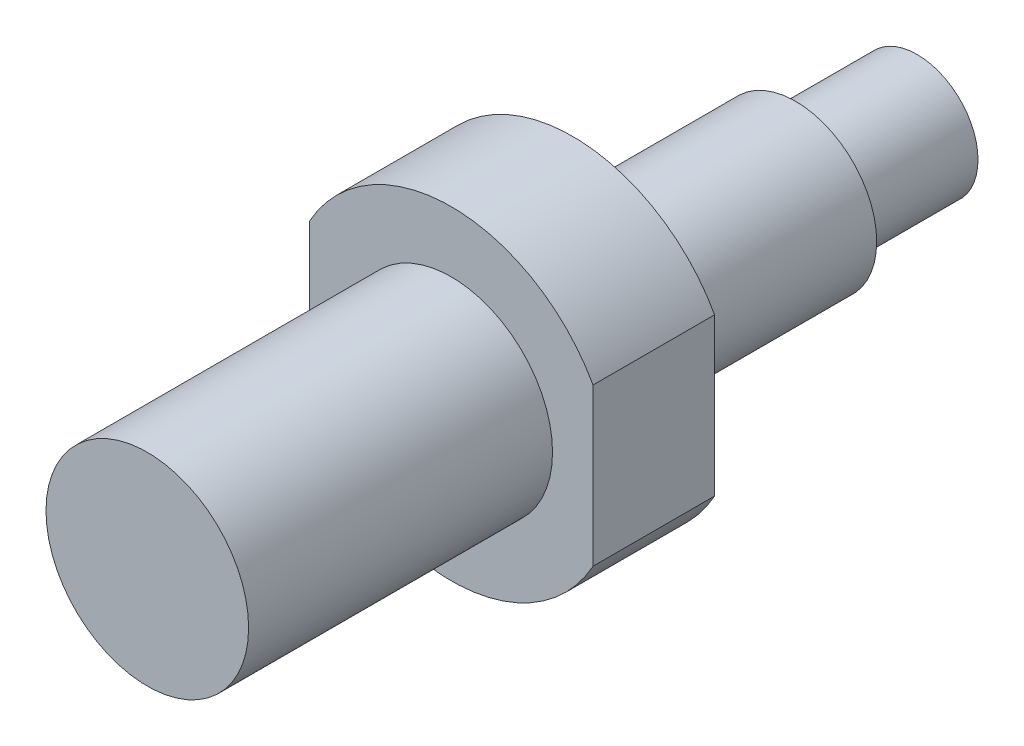
SolidWorks part; units mm, degrees
material "普通碳钢"
ref_plane "前视基准面" through (0, 0, 0) normal (0, 0, 1) x (1, 0, 0)
ref_plane "上视基准面" through (0, 0, 0) normal (0, 1, 0) x (1, 0, 0)
ref_plane "右视基准面" through (0, 0, 0) normal (1, 0, 0) x (0, 0, -1)
sketch "草图2" plane through (0, 0, 0) normal (1, 0, 0) x (0, 0, -1)
  line L0 (0, 0) -> (128.8801, 0) construction
  line L1 (0, 0) -> (0, 5)
  line L2 (0, 5) -> (15, 5)
  line L7 (15, 5) -> (15, 9)
  line L8 (15, 9) -> (21, 9)
  line L9 (21, 9) -> (21, 4)
  line L10 (21, 4) -> (32, 4)
  line L11 (32, 4) -> (32, 0)
  line L12 (0, 0) -> (32, 0)
  dimension "D1" = 15
  dimension "D2" = 5
  dimension "D6" = 6
  dimension "D7" = 4
  dimension "D8" = 9
  dimension "D9" = 11
revolve "旋转1" add sketch "草图2" angle 360 about L0
cosmetic thread "装饰螺纹线1" parameters "D1"=11, "D2"=7
sketch "草图3" plane through (0, 0, -15) normal (0, 0, 1) x (1, 0, 0)
  line L0 (0, 0) -> (0, -7.8258) construction
  line L1 (-7, 8.3859) -> (-15, 8.3859)
  line L2 (7, -8.438) -> (15, -8.438)
  line L3 (7, -8.438) -> (7, 8.3859)
  line L4 (7, 8.3859) -> (15, 8.3859)
  line L5 (15, -8.438) -> (15, 8.3859)
  line L6 (-7, -8.438) -> (-15, -8.438)
  line L7 (-7, -8.438) -> (-7, 8.3859)
  line L8 (-15, -8.438) -> (-15, 8.3859)
  dimension "D1" = 7
  dimension "D2" = 8
extrude "切除-拉伸1" cut sketch "草图3" against normal blind 10
sketch "草图5" plane through (0, 0, -21) normal (0, 0, -1) x (-1, 0, 0)
  circle A0 centre (0, 0) radius 8
  dimension "D1" = 16
extrude "切除-拉伸2" cut sketch "草图5" against normal blind 10 flip side to cut
ref_axis "基准轴1" through (0, 0, -32) along (0, 0, 1)
sketch "草图6" plane through (0, 0, -32) normal (0, 0, -1) x (-1, 0, 0)
  circle A0 centre (0, 0) radius 3
  dimension "D1" = 6
extrude "凸台-拉伸1" add sketch "草图6" along normal blind 6
cosmetic thread "装饰螺纹线2" parameters "D1"=6, "D2"=5
